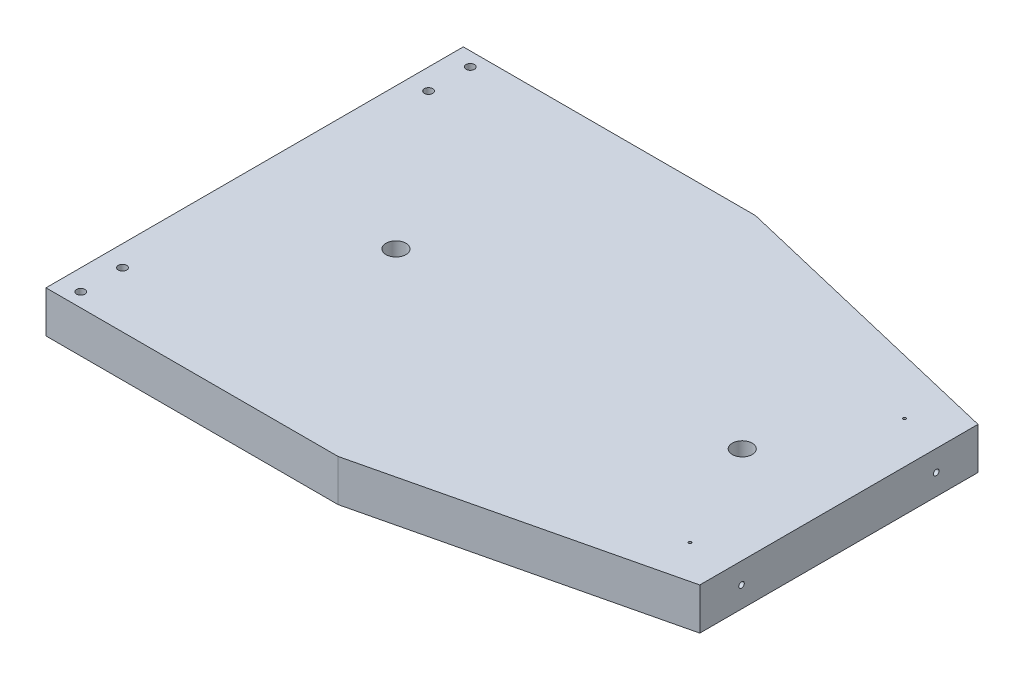
SolidWorks part; units mm, degrees
material "Carvalho"
ref_plane "Plano frontal" through (0, 0, 0) normal (0, 0, 1) x (1, 0, 0)
ref_plane "Plano superior" through (0, 0, 0) normal (0, 1, 0) x (1, 0, 0)
ref_plane "Plano direito" through (0, 0, 0) normal (1, 0, 0) x (0, 0, -1)
sketch "Esboço1" plane through (0, 0, 0) normal (0, 1, 0) x (1, 0, 0)
  line L0 (210, 50) -> (105, 75)
  line L1 (0, -75) -> (105, -75)
  line L2 (0, -75) -> (0, 75)
  line L3 (0, 75) -> (105, 75)
  line L4 (210, -50) -> (210, 50)
  line L5 (195, -38.5714) -> (210, -38.5714) construction
  line L6 (195, -38.5714) -> (195, -53.5714) construction
  line L7 (105, -75) -> (210, -50)
  line L8 (-14.8259, 0) -> (14.392, 0) construction
  line L9 (0, 21.2472) -> (0, -16.7598) construction
  circle A0 centre (50.8, 0) radius 3.5719
  circle A1 centre (175.26, 0) radius 3.57
  circle A2 centre (7.5, -70) radius 1.5
  circle A3 centre (7.5, -55) radius 1.5
  circle A4 centre (7.5, 55) radius 1.5
  circle A5 centre (7.5, 70) radius 1.5
  circle A6 centre (195, -38.5714) radius 0.5
  circle A7 centre (195, 38.5714) radius 0.5
  point P0 (0, 0)
  dimension "D3" = 7.1437
  dimension "D5" = 7.14
  dimension "D9" = 1
  dimension "D1" = 25
  dimension "D2" = 150
  dimension "D4" = 50.8
  dimension "D6" = 210
  dimension "D7" = 175.26
  dimension "D8" = 105
  dimension "D10" = 15
  dimension "D11" = 15
extrude "Ressalto-extrusão1" add sketch "Esboço1" along normal blind 15
sketch "Esboço2" plane through (210, 0, 0) normal (1, 0, 0) x (0, 0, -1)
  line L0 (0, 0) -> (0, 15) construction
  line L1 (-50, 0) -> (50, 0) construction
  line L2 (-50, 15) -> (50, 15) construction
  circle A0 centre (-35, 7.5) radius 1
  circle A1 centre (35, 7.5) radius 1
  point P8 (0, 7.5)
  dimension "D2" = 2
  dimension "D1" = 35
extrude "Corte-extrusão1" cut sketch "Esboço2" against normal blind 10
